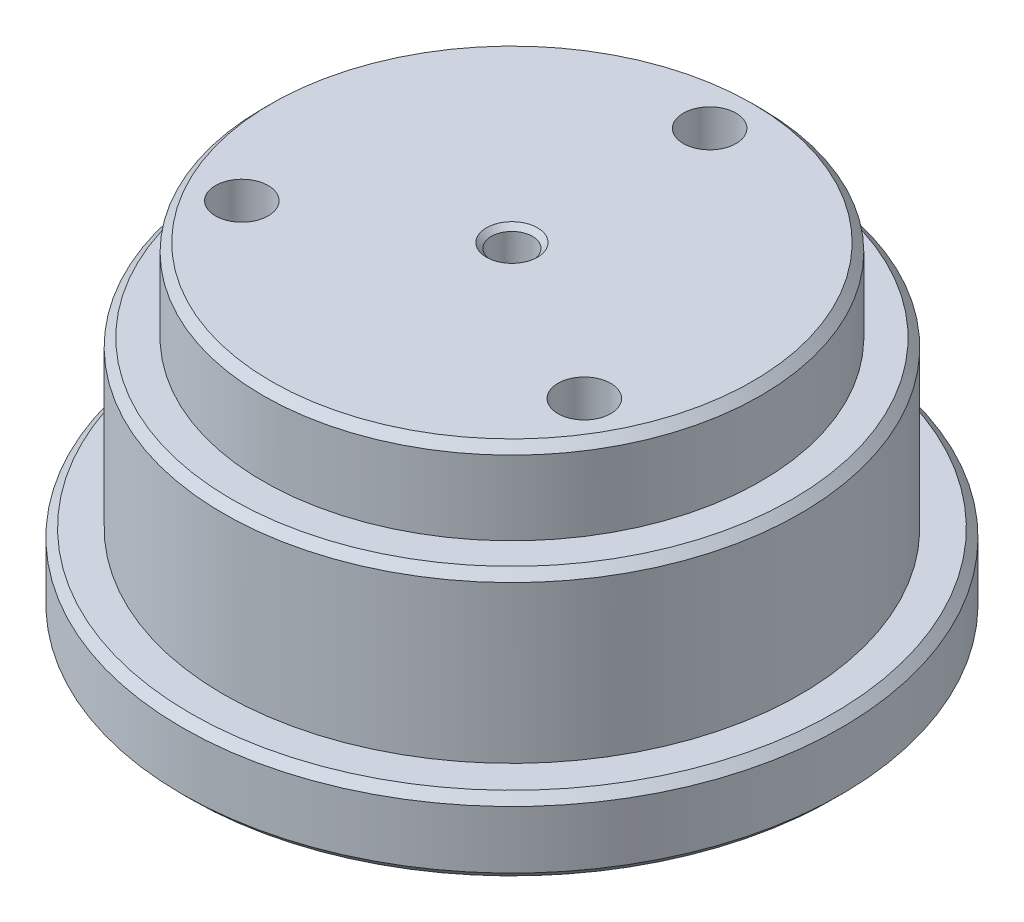
SolidWorks part; units mm, degrees
ref_plane "Front" through (0, 0, 0) normal (0, 0, 1) x (1, 0, 0)
ref_plane "Top" through (0, 0, 0) normal (0, 1, 0) x (1, 0, 0)
ref_plane "Right" through (0, 0, 0) normal (1, 0, 0) x (0, 0, -1)
sketch "Эскиз1" plane through (0, 0, 0) normal (0, 1, 0) x (1, 0, 0)
  circle A0 centre (0, 0) radius 20
  dimension "D1" = 40
extrude "Бобышка-Вытянуть1" add sketch "Эскиз1" along normal blind 19.5
sketch "Эскиз2" plane through (0, 0, 0) normal (0, 1, 0) x (1, 0, 0)
  circle A0 centre (0, 0) radius 17.5
  dimension "D1" = 35
extrude "Вырез-Вытянуть1" cut sketch "Эскиз2" along normal through all from offset 4.5 flip side to cut
sketch "Эскиз3" plane through (0, 0, 0) normal (0, -1, 0) x (1, 0, 0)
  circle A0 centre (0, 0) radius 15.1
  dimension "D1" = 30.2
extrude "Вырез-Вытянуть2" cut sketch "Эскиз3" against normal blind 6 from offset 14.5 flip side to cut offset against normal yes
sketch "Эскиз4" plane through (0, 0, 0) normal (0, 1, 0) x (1, 0, 0)
  circle A0 centre (0, 0) radius 1.25
  circle A1 centre (0, 0) radius 12 construction
  circle A2 centre (0, 12) radius 1.6
  circle A3 centre (0, 12) radius 3.25
  circle A4 centre (0, 0) radius 3
  dimension "D1" = 24
  dimension "D2" = 2.5
  dimension "D3" = 3.2
  dimension "D5" = 6
extrude "Вырез-Вытянуть3" cut sketch "Эскиз4" along normal through all contours A0 region at (0, 0, 0)
extrude "Вырез-Вытянуть4" cut sketch "Эскиз4<3>" along normal through all contours A2 region at (0, 0, -12)
sketch "Эскиз4<3>" plane through (0, 0, 0) normal (0, 1, 0) x (1, 0, 0) same geometry as "Эскиз4"
extrude "Вырез-Вытянуть5" cut sketch "Эскиз4<4>" along normal blind 4 contours A2 region at (-3.1581, 0, -12)
sketch "Эскиз4<4>" plane through (0, 0, 0) normal (0, 1, 0) x (1, 0, 0) same geometry as "Эскиз4"
pattern_circular "Круговой массив1" count 3 over 360 about axis through (0, 19.5, 0) along (0, -1, 0) of "Вырез-Вытянуть5", "Вырез-Вытянуть4" reverse direction yes
chamfer "Фаска1" distance 0.5 angle 45 4 edges at (0, 4.5, 20) (0, 0, 20) (0, 19.5, 15.1) (0, 14.5, -17.5)
extrude "Вырез-Вытянуть6" cut sketch "Эскиз4<5>" along normal blind 4 contours A4 A0 region at (-2.9151, 0, 0)
sketch "Эскиз4<5>" plane through (0, 0, 0) normal (0, 1, 0) x (1, 0, 0) same geometry as "Эскиз4"
chamfer "Фаска2" distance 0.3 angle 45 2 edges at (0, 19.5, 1.25) (0, 0, 3)
